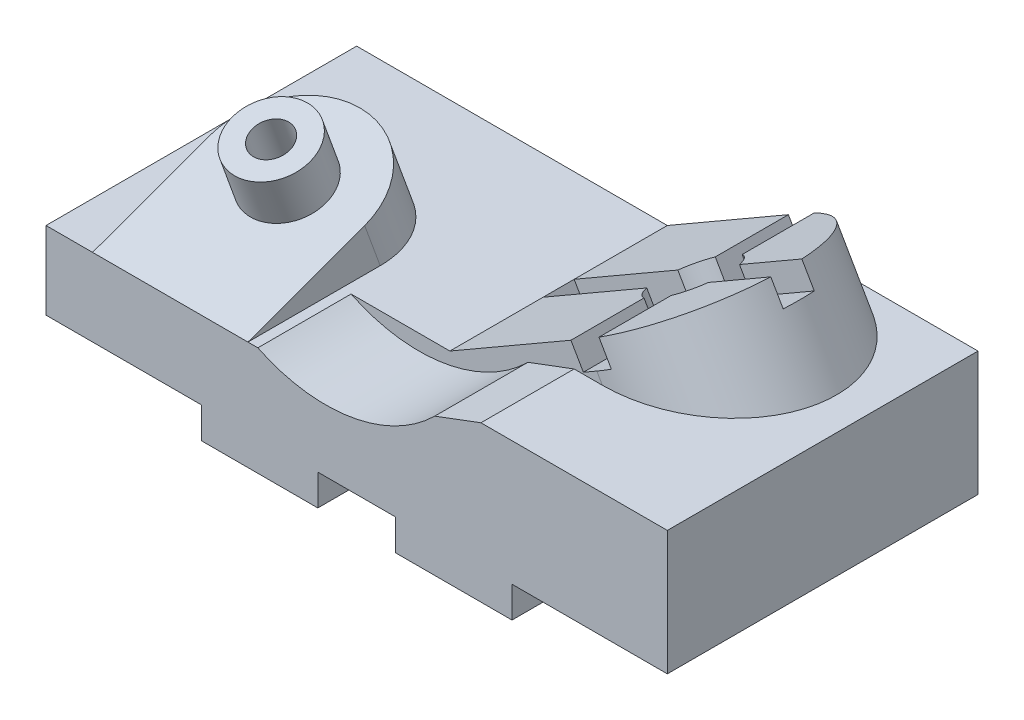
SolidWorks part; units mm, degrees
ref_plane "Front Plane" through (0, 0, 0) normal (0, 0, 1) x (1, 0, 0)
ref_plane "Top Plane" through (0, 0, 0) normal (0, 1, 0) x (1, 0, 0)
ref_plane "Right Plane" through (0, 0, 0) normal (1, 0, 0) x (0, 0, -1)
sketch "Sketch4" plane through (0, 0, 0) normal (0, 0, 1) x (1, 0, 0)
  line L0 (0, 0) -> (50, 0)
  line L1 (50, 0) -> (50, -10)
  line L2 (50, -10) -> (87.5, -10)
  line L3 (87.5, -10) -> (87.5, 0)
  line L4 (87.5, 0) -> (112.5, 0)
  line L5 (112.5, 0) -> (112.5, -10)
  line L6 (112.5, -10) -> (150, -10)
  line L7 (150, -10) -> (150, 0)
  line L8 (150, 0) -> (200, 0)
  line L9 (200, 0) -> (200, 40)
  line L10 (200, 40) -> (140, 40)
  line L11 (140, 40) -> (100, 25)
  line L12 (100, 25) -> (0, 25)
  line L13 (0, 25) -> (0, 0)
  dimension "D1" = 200
  dimension "D2" = 37.5
  dimension "D3" = 50
  dimension "D4" = 25
  dimension "D5" = 10
  dimension "D6" = 25
  dimension "D7" = 40
  dimension "D8" = 60
  dimension "D9" = 100
extrude "Boss-Extrude3" add sketch "Sketch4" along normal blind 100
ref_plane "Plane1" through (0, 54.2149, 19.7326) normal (0, 0.9397, 0.342) x (-1, 0, 0)
sketch "Sketch5" plane through (0, 54.2149, 19.7326) normal (0, 0.9397, 0.342) x (-1, 0, 0)
  line L0 (-15, 85.4188) -> (-15, 45.4188)
  line L1 (-100, 85.4188) -> (0, 85.4188) construction
  line L2 (-65, 45.4188) -> (-65, 85.4188)
  line L3 (-65, 85.4188) -> (-15, 85.4188)
  line L4 (0, 85.4188) -> (0, -8.5505) construction
  arc A0 (-15, 45.4188) -> (-65, 45.4188) centre (-40, 45.4188) cw
  circle A1 centre (-40, 45.4188) radius 6
  circle A2 centre (-40, 45.4188) radius 12.5
  dimension "D3" = 25
  dimension "D4" = 12
  dimension "D5" = 25
  dimension "D1" = 15
  dimension "D2" = 40
extrude "Boss-Extrude4" add sketch "Sketch5" against normal up to surface (14.5588 mm away) contours L0 A0 L2 L3 up to face at (50, 25, 50)
extrude "Boss-Extrude5" add sketch "Sketch5<4>" along normal blind 15 contours A2 A1 region at (52.1464, 38.6808, 62.4123)
sketch "Sketch5<4>" plane through (0, 54.2149, 19.7326) normal (0, 0.9397, 0.342) x (-1, 0, 0) same geometry as "Sketch5"
sketch "Sketch7" plane through (0, 54.2149, 19.7326) normal (0, 0.9397, 0.342) x (1, 0, 0)
  circle A1 centre (40, -45.4188) radius 6
  circle A2 centre (40, -45.4188) radius 6
  dimension "D1" = 0
extrude "Cut-Extrude1" cut sketch "Sketch7" against normal through all
ref_plane "Plane2" through (14.1747, -24.5513, 0) normal (0.5, -0.866, 0) x (0, 0, -1)
sketch "Sketch8" plane through (14.1747, -24.5513, 0) normal (0.5, -0.866, 0) x (0, 0, -1)
  line L0 (0, 99.1025) -> (0, 149.1025)
  line L1 (0, 193.2051) -> (0, 141.2436) construction
  line L2 (-70, 149.1025) -> (-70, 99.1025)
  line L3 (-100, 99.1025) -> (0, 99.1025) construction
  line L4 (-70, 99.1025) -> (0, 99.1025)
  arc A0 (0, 149.1025) -> (-70, 149.1025) centre (-35, 149.1025) ccw
  dimension "D2" = 35
  dimension "D1" = 50
extrude "Boss-Extrude7" add sketch "Sketch8" along normal blind 35 contours L2 L4 L0 A0
sketch "Sketch9" plane through (14.1747, -24.5513, 0) normal (-0.5, 0.866, 0) x (0.866, 0.5, 0)
  line L0 (99.1025, -35) -> (184.1025, -35) construction
  line L1 (99.1025, -70) -> (99.1025, 0) construction
  line L2 (149.1025, 0) -> (149.1025, -70) construction
  line L3 (99.1025, 0) -> (149.1025, 0) construction
  line L4 (141.2436, -70) -> (149.1025, -70) construction
  line L5 (149.1025, -70) -> (99.1025, -70) construction
  line L6 (99.1025, -40) -> (137.6461, -40)
  line L7 (144.1025, 0) -> (144.1025, -23.5436)
  line L8 (99.1025, -30) -> (137.6461, -30)
  line L9 (154.1025, 0) -> (154.1025, -23.5436)
  line L10 (99.1025, -30) -> (99.1025, -40)
  line L11 (144.1025, 0) -> (154.1025, 0)
  line L12 (184.1025, -30) -> (184.1025, -40)
  line L13 (144.1025, -70) -> (154.1025, -70)
  line L14 (154.1025, -46.4564) -> (154.1025, -70)
  line L15 (160.559, -30) -> (184.1025, -30)
  line L16 (154.1025, 0) -> (154.1025, -70) construction
  line L18 (99.1025, -30) -> (184.1025, -30) construction
  line L19 (160.559, -40) -> (184.1025, -40)
  line L20 (144.1025, 0) -> (144.1025, -70) construction
  line L21 (144.0439, -46.4306) -> (144.1025, -70)
  line L22 (99.1025, -40) -> (184.1025, -40) construction
  arc A0 (149.1025, -70) -> (149.1025, 0) centre (149.1025, -35) ccw construction
  arc A1 (144.1025, -23.5436) -> (137.6461, -30) centre (149.1025, -35) ccw
  arc A2 (160.559, -30) -> (154.1025, -23.5436) centre (149.1025, -35) ccw
  arc A3 (137.6461, -40) -> (144.0439, -46.4306) centre (149.1025, -35) ccw
  arc A4 (154.1025, -46.4564) -> (160.559, -40) centre (149.1025, -35) ccw
  point P31 (144.0439, -70)
  dimension "D1" = 25
  dimension "D2" = 50
  dimension "D3" = 5
  dimension "D4" = 5
extrude "Cut-Extrude2" cut sketch "Sketch9" against normal blind 8
sketch "Sketch10" plane through (0, 0, 100) normal (0, 0, 1) x (1, 0, 0)
  line L0 (100, 25) -> (65, 25) construction
  line L1 (66.1688, 26.0446) -> (66.1688, 113.9554)
  arc A0 (66.1688, 26.0446) -> (66.1688, 113.9554) centre (90, 70) ccw
  dimension "D1" = 100
  dimension "D3" = 110
  dimension "D2" = 45
  dimension "D4" = 23.8312
extrude "Cut-Extrude3" cut sketch "Sketch10" against normal up to surface (30 mm away) up to face at (136.3864, 39.3573, 70)
